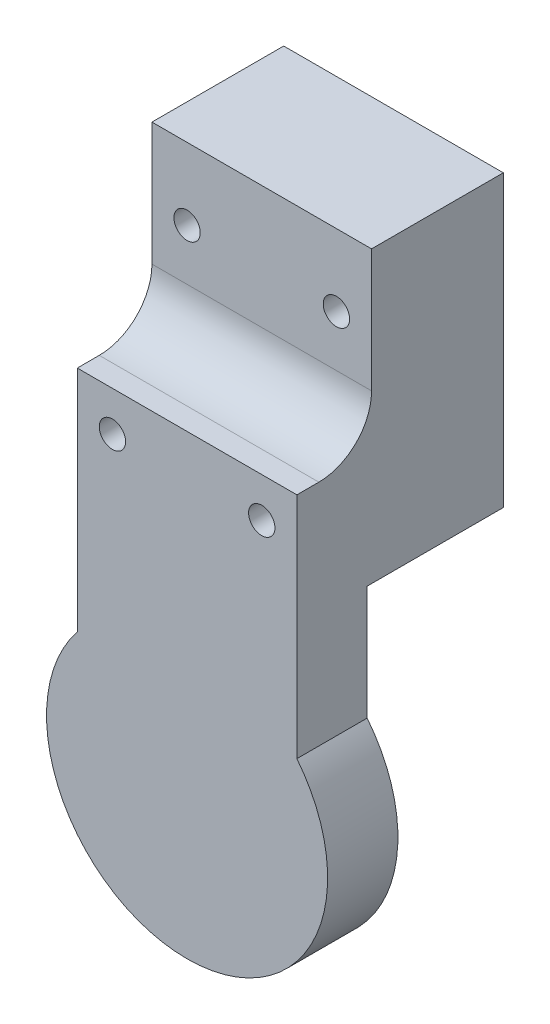
SolidWorks part; units mm, degrees
ref_plane "Front Plane" through (0, 0, 0) normal (0, 0, 1) x (1, 0, 0)
ref_plane "Top Plane" through (0, 0, 0) normal (0, 1, 0) x (1, 0, 0)
ref_plane "Right Plane" through (0, 0, 0) normal (1, 0, 0) x (0, 0, -1)
sketch "Sketch1" plane through (0, 0, 0) normal (0, 0, 1) x (1, 0, 0)
  line L0 (-5.5, 5.8095) -> (-5.5, -2.5)
  line L1 (-5.5, -2.5) -> (-2.5, -5.5)
  line L2 (-2.5, -5.5) -> (2.5, -5.5)
  line L3 (2.5, -5.5) -> (5.5, -2.5)
  line L4 (5.5, -2.5) -> (5.5, 5.8095)
  line L5 (5.5, 6.5) -> (4.6637, 6.5) construction
  line L6 (-5.5, 6.5) -> (-5.5, 5.8095) construction
  line L7 (-4.6637, 6.5) -> (-5.5, 6.5) construction
  line L8 (4.6637, 6.5) -> (-4.6637, 6.5) construction
  line L9 (5.5, 5.8095) -> (5.5, 6.5) construction
  arc A0 (-5.5, 5.8095) -> (5.5, 5.8095) centre (0, 0) ccw
  arc A1 (-4.6637, 6.5) -> (-5.5, 5.8095) centre (0, 0) ccw construction
  arc A2 (4.6637, 6.5) -> (-4.6637, 6.5) centre (0, 0) ccw construction
  arc A3 (5.5, 5.8095) -> (4.6637, 6.5) centre (0, 0) ccw construction
  dimension "D1" = 16
extrude "Boss-Extrude1" add sketch "Sketch1" along normal blind 1.4
sketch "Sketch2" plane through (0, 0, 1.4) normal (0, 0, 1) x (1, 0, 0)
  line L0 (1, -5.5) -> (-1, -5.5) construction
  line L1 (2.5, -5.5) -> (-2.5, -5.5) construction
  line L2 (-1, -5.5) -> (-1, -6.5)
  line L3 (-1, -6.5) -> (1, -6.5)
  line L4 (1, -6.5) -> (1, -5.5)
  line L5 (-5.5, -2.5) -> (-5.5, 5.8095)
  line L6 (-5.5, -2.5) -> (-2.5, -5.5)
  line L7 (-2.5, -5.5) -> (-5.5, -2.5) construction
  line L8 (-2.5, -5.5) -> (-1, -5.5)
  line L9 (2.5, -5.5) -> (5.5, -2.5)
  line L10 (5.5, -2.5) -> (5.5, 5.8095)
  line L11 (5.5, 5.8095) -> (5.5, -2.5) construction
  line L12 (1, -5.5) -> (2.5, -5.5)
  line L13 (-1, -5.5) -> (1, -5.5) construction
  arc A0 (-5.5, 5.8095) -> (5.5, 5.8095) centre (0, 0) ccw
  arc A1 (5.5, 5.8095) -> (-5.5, 5.8095) centre (0, 0) ccw construction
  point P5 (0, -5.5)
  dimension "D1" = 2
  dimension "D2" = 1
extrude "Boss-Extrude2" add sketch "Sketch2" along normal up to surface (0.7 mm away)
sketch "Sketch3" plane through (0, 0, 2.1) normal (0, 0, 1) x (1, 0, 0)
  line L1 (-1, -5.5) -> (-1, -6.5)
  line L2 (-1, -6.5) -> (1, -6.5)
  line L3 (1, -6.5) -> (1, -5.5)
  line L4 (1, -5.5) -> (-1, -5.5)
  line L6 (-5.5, 5.8095) -> (-5.5, 6.5)
  line L7 (-5.5, 6.5) -> (5.5, 6.5)
  line L8 (5.5, 6.5) -> (5.5, 5.8095)
  circle A0 centre (0, 0) radius 2.5
  arc A1 (-5, 5.5) -> (-3.5, 5.5) centre (-4.25, 5.5) ccw
  arc A2 (3.5, 5.5) -> (5, 5.5) centre (4.25, 5.5) ccw
  arc A3 (-5.5, 5.8095) -> (5.5, 5.8095) centre (0, 0) ccw
  arc A4 (-5.5, 5.8095) -> (5.5, 5.8095) centre (0, 0) ccw construction
  arc A5 (-3.5, 5.5) -> (-5, 5.5) centre (-4.25, 5.5) ccw
  arc A6 (5, 5.5) -> (3.5, 5.5) centre (4.25, 5.5) ccw
  circle M1 centre (-4.25, 5.5) radius 0.5
  circle M2 centre (4.25, 5.5) radius 0.5
  line M3 (5.5, -2.5) -> (5.5, 6.5)
  line M4 (5.5, 6.5) -> (-5.5, 6.5)
  line M5 (-5.5, 6.5) -> (-5.5, -2.5)
  line M6 (-5.5, -2.5) -> (-2.5, -5.5)
  line M7 (-2.5, -5.5) -> (2.5, -5.5)
  line M8 (2.5, -5.5) -> (5.5, -2.5)
  circle M9 centre (0, 0) radius 2.5
  dimension "D1" = 5
  dimension "D2" = 1.5
extrude "Boss-Extrude3" add sketch "Sketch3" along normal up to surface (0.6 mm away) contours M8 M3 M4 M5 M6 M7 M2 M9 M1 | A3 L3 L2 L1 M5 M3 M8 M7 M6
sketch "Sketch4" plane through (0, 0, 2.7) normal (0, 0, 1) x (1, 0, 0)
  line L0 (-1, -5.5) -> (-1, -6.5)
  line L1 (-1, -6.5) -> (1, -6.5)
  line L2 (1, -6.5) -> (1, -5.5)
  line L3 (1, -5.5) -> (-1, -5.5)
  line L4 (-5.5, 5.8095) -> (-5.5, 6.5)
  line L5 (-5.5, 6.5) -> (5.5, 6.5)
  line L6 (5.5, 6.5) -> (5.5, 5.8095)
  circle A0 centre (0, 0) radius 2
  circle A1 centre (-4.25, 5.5) radius 0.75
  circle A2 centre (4.25, 5.5) radius 0.75
  arc A3 (-5.5, 5.8095) -> (5.5, 5.8095) centre (0, 0) ccw
  arc A4 (-4.6637, 6.5) -> (-5.5, 5.8095) centre (0, 0) ccw construction
  arc A5 (4.6637, 6.5) -> (-4.6637, 6.5) centre (0, 0) ccw construction
  arc A6 (5.5, 5.8095) -> (4.6637, 6.5) centre (0, 0) ccw construction
  circle A7 centre (-4.25, 5.5) radius 0.75 construction
  circle A8 centre (4.25, 5.5) radius 0.75 construction
  dimension "D1" = 4
extrude "Boss-Extrude4" add sketch "Sketch4" along normal blind 1.3
sketch "Sketch5" plane through (0, 0, 0) normal (0, 0, 1) x (1, 0, 0)
  line L0 (-8, 0) -> (-6.25, 0) construction
  line L1 (8, 0) -> (6.25, 0) construction
  line L2 (-6.25, 0) -> (-6.25, 18) construction
  line L3 (6.25, 0) -> (6.25, 18) construction
  line L4 (-6.25, 4.9937) -> (-6.25, 18)
  line L5 (6.25, 4.9937) -> (6.25, 18)
  line L6 (-5.5, 5.8095) -> (-5.5, 6.5)
  line L7 (-5.5, 6.5) -> (-4.25, 6.5) construction
  line L8 (5.5, 6.5) -> (5.5, 5.8095)
  line L9 (-6.25, 18) -> (6.25, 18)
  line L10 (4.25, -994.5) -> (4.25, 6.5) construction
  line L11 (-4.25, -994.5) -> (-4.25, 6.5) construction
  line L12 (4.25, 6.5) -> (4.25, 8.5) construction
  line L13 (4.25, 8.5) -> (-4.25, 8.5) construction
  line L14 (-4.25, 8.5) -> (-4.25, 6.5) construction
  line L15 (-4.25, 6.5) -> (4.25, 6.5) construction
  line L16 (4.25, 6.5) -> (5.5, 6.5) construction
  line L17 (4.25, 6.5) -> (4.25, 8.5) construction
  line L18 (4.25, 8.5) -> (4.25, 49005.5) construction
  line L19 (-4.25, 6.5) -> (-4.25, 8.5) construction
  line L20 (-4.25, 8.5) -> (-4.25, 49005.5) construction
  line L21 (4.25, 8.5) -> (5.5, 6.5)
  line L22 (-4.25, 8.5) -> (-5.5, 6.5)
  arc A0 (-5.5, 5.8095) -> (5.5, 5.8095) centre (0, 0) ccw construction
  arc A1 (6.25, 4.9937) -> (5.5, 5.8095) centre (0, 0) ccw
  arc A2 (-5.5, 5.8095) -> (-6.25, 4.9937) centre (0, 0) ccw
  arc A3 (4.25, 8.5) -> (-4.25, 8.5) centre (0, 0) ccw
  dimension "D1" = 1.75
  dimension "D2" = 1.75
  dimension "D3" = 18
  dimension "D4" = 2
extrude "Boss-Extrude6" add sketch "Sketch5" along normal up to surface (4 mm away) up to face at (-3.5, 5.5, 4)
chamfer "Chamfer1" distance 2 angle 45 1 edges at (0, 9.5033, 0)
ref_plane "Plane1" through (0, 0, -7.75) normal (0, 0, 1) x (1, 0, 0)
sketch "Sketch7" plane through (0, 0, 0) normal (0, 0, -1) x (-1, 0, 0)
  line L0 (6.25, 4.9937) -> (6.25, 18) construction
  line L1 (-6.25, 18) -> (6.25, 18)
  line L2 (-6.25, 18) -> (-6.25, 11.4969)
  line L3 (-6.25, 11.4969) -> (6.25, 11.4969)
  line L4 (6.25, 18) -> (6.25, 11.4969)
extrude "Boss-Extrude7" add sketch "Sketch7" along normal up to surface (7.75 mm away) up to plane "Plane1"
sketch "Sketch8" plane through (0, 18, 0) normal (0, 1, 0) x (1, 0, 0)
  line L1 (6.25, 7.75) -> (-6.25, 7.75)
  line L2 (6.25, 7.75) -> (6.25, 0.25)
  line L3 (6.25, 0.25) -> (-6.25, 0.25)
  line L4 (-6.25, 7.75) -> (-6.25, 0.25)
  line L5 (-6.25, -4) -> (-6.25, 7.75) construction
  dimension "D1" = 7.5
extrude "Boss-Extrude8" add sketch "Sketch8" along normal blind 10
fillet "Fillet1" radius 3 1 edges at (0, 18, -0.25)
sketch "Sketch9" plane through (0, 6.5, 0) normal (0, 1, 0) x (1, 0, 0)
  line L1 (5.5, -4) -> (-5.5, -4)
  line L2 (5.5, -4) -> (5.5, -2.1)
  line L3 (5.5, -2.1) -> (-5.5, -2.1)
  line L4 (-5.5, -4) -> (-5.5, -2.1)
extrude "Boss-Extrude9" add sketch "Sketch9" along normal up to vertex
sketch "Sketch10" plane through (0, 0, 4) normal (0, 0, 1) x (1, 0, 0)
  line L1 (1, -5.5) -> (-1, -5.5)
  line L2 (1, -5.5) -> (1, -6.5)
  line L3 (1, -6.5) -> (-1, -6.5)
  line L4 (-1, -5.5) -> (-1, -6.5)
  circle A0 centre (4.25, 5.5) radius 0.75
  circle A1 centre (-4.25, 5.5) radius 0.75
  circle A2 centre (0, 0) radius 2
  circle A3 centre (-4.25, 5.5) radius 0.75 construction
  circle A4 centre (4.25, 5.5) radius 0.75 construction
extrude "Boss-Extrude10" add sketch "Sketch10" against normal blind 0.75
sketch "Sketch11" plane through (0, 0, -7.75) normal (0, 0, -1) x (-1, 0, 0)
  line L0 (0, 11.4969) -> (0, 28) construction
  line L1 (6.25, 11.4969) -> (-6.25, 11.4969) construction
  line L3 (-6.25, 19.7484) -> (6.25, 19.7484) construction
  line L4 (-6.25, 11.4969) -> (-6.25, 28) construction
  line L6 (6.25, 11.4969) -> (-6.25, 19.7484) construction
  line L7 (-6.25, 19.7484) -> (6.25, 28) construction
  line L9 (6.25, 28) -> (6.25, 11.4969) construction
  line L10 (-6.25, 28) -> (6.25, 28) construction
  circle A0 centre (0, 15.6227) radius 2
  circle A1 centre (0, 23.8742) radius 2
  dimension "D1" = 4
extrude "Boss-Extrude11" add sketch "Sketch11" along normal blind 2.5
fillet "Fillet2" radius 2.5 2 edges at (-2, 23.8742, -10.25) (-2, 15.6227, -10.25)
sketch "Sketch12" plane through (0, 0, -7.75) normal (0, 0, -1) x (-1, 0, 0)
  line L0 (6, 15.7375) -> (-6.25, 15.7375) construction
  line L1 (-6.25, 11.4969) -> (-6.25, 28) construction
  line L2 (6, 23.9125) -> (-6.25, 23.9125) construction
  line L3 (6.25, 28) -> (6.25, 11.4969) construction
  circle A0 centre (-4.25, 15.7375) radius 0.75
  circle A1 centre (-4.25, 23.9125) radius 0.75
  circle A2 centre (4.25, 23.9125) radius 0.75
  circle A3 centre (4.25, 15.7375) radius 0.75
  point P6 (-0.125, 15.7375)
  point P10 (-0.125, 23.9125)
  dimension "D1" = 1.5
  dimension "D2" = 2
  dimension "D3" = 2
extrude "Cut-Extrude1" cut sketch "Sketch12" against normal through all both and the other way through all
sketch "Sketch13" plane through (5.5, 0, 0) normal (-1, 0, 0) x (0, 0, 1)
  line L1 (2.1, 6.5) -> (0, 6.5)
  line L2 (2.1, 6.5) -> (2.1, 7.5)
  line L3 (2.1, 7.5) -> (0, 7.5)
  line L4 (0, 6.5) -> (0, 7.5)
  dimension "D1" = 1
extrude "Cut-Extrude2" cut sketch "Sketch13" along normal up to surface (11 mm away) up to face at (-5.5, 2, 1.05)
